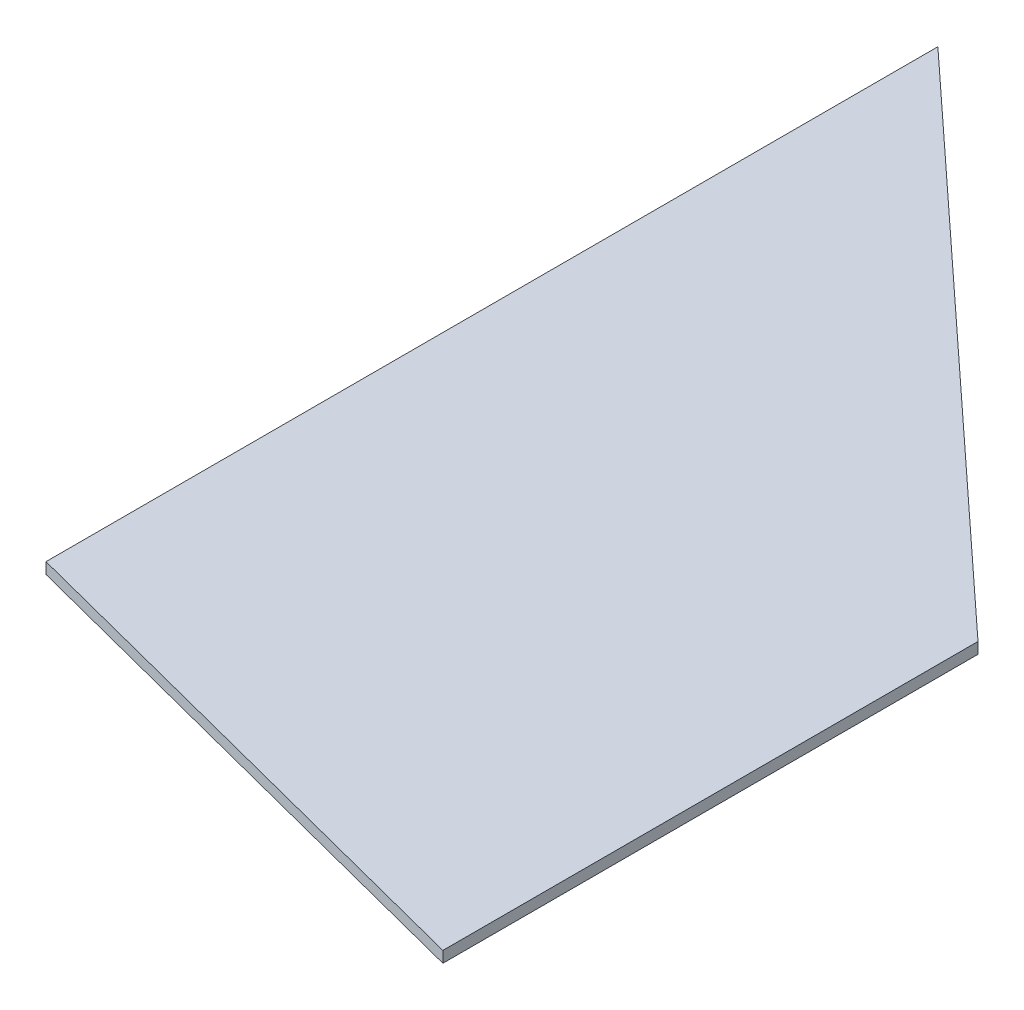
SolidWorks part; units mm, degrees
material "Balsa"
ref_plane "Front Plane" through (0, 0, 0) normal (0, 0, 1) x (1, 0, 0)
ref_plane "Top Plane" through (0, 0, 0) normal (0, 1, 0) x (1, 0, 0)
ref_plane "Right Plane" through (0, 0, 0) normal (1, 0, 0) x (0, 0, -1)
sketch "Sketch1" plane through (0, 0, 0) normal (0, 1, 0) x (1, 0, 0)
  line L0 (0, 0) -> (0, 254)
  line L1 (0, 254) -> (152.4, 113.03)
  line L2 (152.4, 113.03) -> (152.4, -39.37)
  line L3 (152.4, -39.37) -> (0, 0)
  point P4 (0, 0)
  point P8 (-0.4837, 260.1847)
  point P9 (137.9409, 218.9844)
  dimension "D1" = 254
  dimension "D2" = 152.4
  dimension "D3" = 152.4
  dimension "D4" = 140.97
extrude "Boss-Extrude1" add sketch "Sketch1" along normal blind 3.175
equation "\"1o\"=3.16863"
